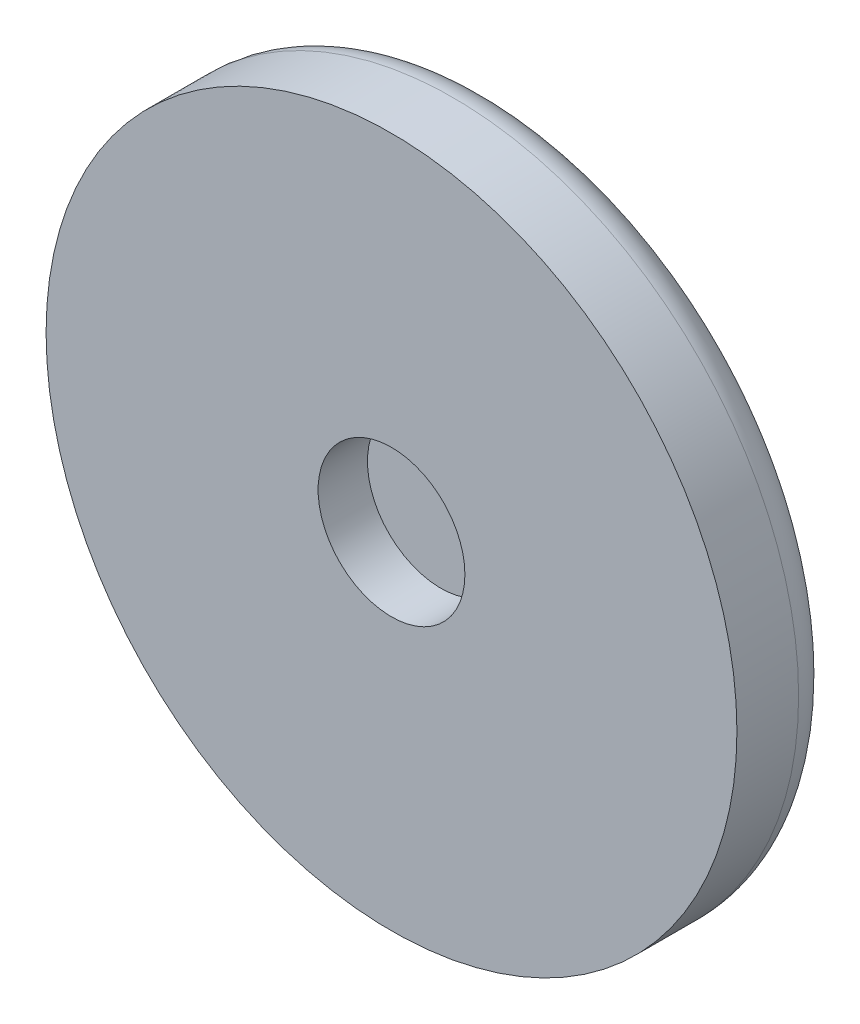
SolidWorks part; units mm, degrees
ref_plane "Front Plane" through (0, 0, 0) normal (0, 0, 1) x (1, 0, 0)
ref_plane "Top Plane" through (0, 0, 0) normal (0, 1, 0) x (1, 0, 0)
ref_plane "Right Plane" through (0, 0, 0) normal (1, 0, 0) x (0, 0, -1)
sketch "Sketch1" plane through (0, 0, 0) normal (0, 0, 1) x (1, 0, 0)
  circle A0 centre (0, 0) radius 14
  dimension "D1" = 28
extrude "Boss-Extrude1" add sketch "Sketch1" along normal blind 4
sketch "Sketch2" plane through (0, 0, 4) normal (0, 0, 1) x (1, 0, 0)
  circle A0 centre (0, 0) radius 2.975
  dimension "D1" = 5.95
extrude "Cut-Extrude1" cut sketch "Sketch2" against normal blind 2
sketch "Sketch3" plane through (0, 0, 0) normal (0, 0, -1) x (-1, 0, 0)
  circle A0 centre (0, 0) radius 11
  dimension "D1" = 22
extrude "Cut-Extrude2" cut sketch "Sketch3" against normal blind 1
fillet "Fillet1" radius 0.5 2 edges at (-11, 0, 1) (-11, 0, 0)
fillet "Fillet2" radius 1.5 1 edges at (14, 0, 0)
